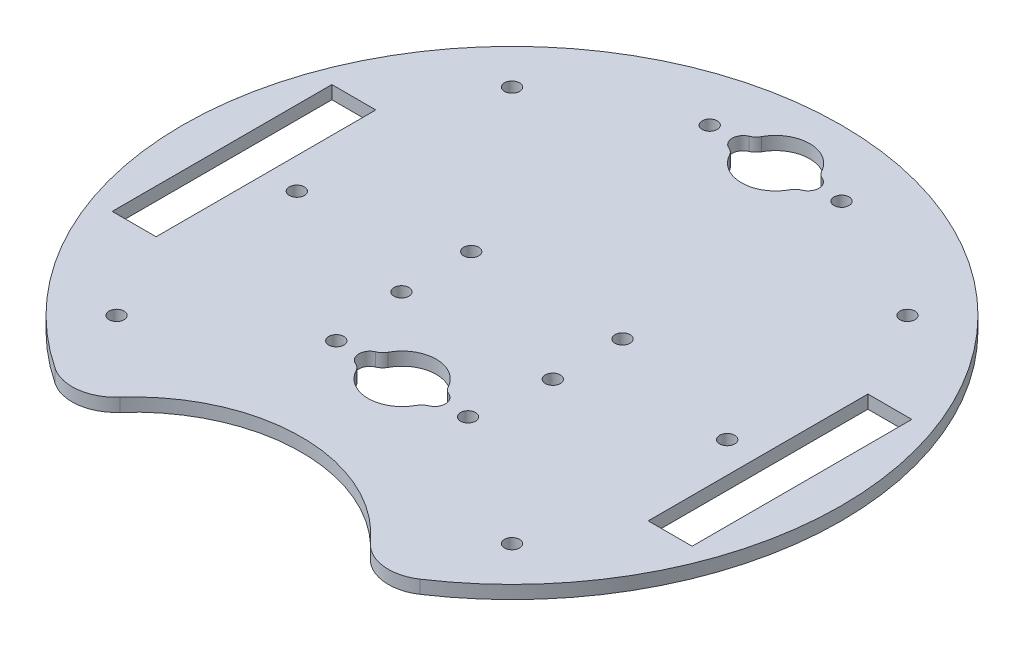
SolidWorks part; units mm, degrees
ref_plane "Front" through (0, 0, 0) normal (0, 0, 1) x (1, 0, 0)
ref_plane "Top" through (0, 0, 0) normal (0, 1, 0) x (1, 0, 0)
ref_plane "Right" through (0, 0, 0) normal (1, 0, 0) x (0, 0, -1)
sketch "Sketch1" plane through (0, 0, 0) normal (0, 1, 0) x (1, 0, 0)
  circle A0 centre (0, 0) radius 75
  dimension "D1" = 150
extrude "Boss-Extrude1" add sketch "Sketch1" along normal blind 3
sketch "Sketch2" plane through (0, 3, 0) normal (0, 1, 0) x (1, 0, 0)
  line L0 (-75, 0) -> (75, 0) construction
  line L2 (-66, -25) -> (-56, -25)
  line L3 (-66, -25) -> (-66, 25)
  line L4 (-66, 25) -> (-56, 25)
  line L5 (-56, -25) -> (-56, 25)
  line L6 (-66, -25) -> (-56, 25) construction
  line L7 (-66, 25) -> (-56, -25) construction
  line L8 (56, -25) -> (66, -25)
  line L9 (56, -25) -> (56, 25)
  line L10 (56, 25) -> (66, 25)
  line L11 (66, -25) -> (66, 25)
  line L12 (56, -25) -> (66, 25) construction
  line L13 (56, 25) -> (66, -25) construction
  circle A0 centre (0, 0) radius 75 construction
  point P5 (-61, 0)
  point P10 (61, 0)
  dimension "D1" = 50
  dimension "D2" = 50
  dimension "D3" = 10
  dimension "D4" = 10
  dimension "D5" = 61
  dimension "D6" = 61
extrude "Cut-Extrude1" cut sketch "Sketch2" against normal blind 6.35
sketch "Sketch3" plane through (0, 3, 0) normal (0, 1, 0) x (1, 0, 0)
  line L0 (0, 60) -> (0, -25) construction
  line L1 (-7.366, -25) -> (7.366, -25) construction
  line L2 (-7.366, 60) -> (7.366, 60) construction
  arc A0 (-7.3358, -27.4998) -> (7.3358, -27.4998) centre (0, -25) ccw
  arc A1 (-7.3358, -22.5002) -> (-7.3358, -27.4998) centre (-7.366, -25) ccw
  arc A2 (7.3358, -27.4998) -> (7.3358, -22.5002) centre (7.366, -25) ccw
  arc A3 (7.3358, -22.5002) -> (-7.3358, -22.5002) centre (0, -25) ccw
  arc A4 (-7.3358, 62.4998) -> (-7.3358, 57.5002) centre (-7.366, 60) ccw
  arc A5 (7.3358, 57.5002) -> (7.3358, 62.4998) centre (7.366, 60) ccw
  arc A6 (7.3358, 62.4998) -> (-7.3358, 62.4998) centre (0, 60) ccw
  arc A8 (-7.3358, 57.5002) -> (7.3358, 57.5002) centre (0, 60) ccw
  dimension "D1" = 15.5
  dimension "D3" = 14.732
  dimension "D4" = 5
  dimension "D2" = 15.5
  dimension "D5" = 5
  dimension "D6" = 60
  dimension "D7" = 25
  dimension "D8" = 14.732
extrude "Cut-Extrude2" cut sketch "Sketch3" against normal blind 10
sketch "Sketch4" plane through (0, 3, 0) normal (0, 1, 0) x (1, 0, 0)
  line L0 (0, 0) -> (0, -86.0323) construction
  line L1 (0, -86.0323) -> (33.1606, -67.2709) construction
  line L3 (-33.1606, -67.2709) -> (0, -86.0323) construction
  circle A0 centre (0, -86.0323) radius 38.1 construction
  circle A1 centre (0, 0) radius 75 construction
  arc A2 (-33.1606, -67.2709) -> (33.1606, -67.2709) centre (0, -86.0323) cw
  arc A3 (-33.1606, -67.2709) -> (33.1606, -67.2709) centre (0, 0) ccw
  dimension "D1" = 76.2
  dimension "D2" = 121
extrude "Cut-Extrude3" cut sketch "Sketch4" against normal blind 10 contours A2 A3
fillet "Fillet2" radius 10 2 edges at (33.1606, 1.5, 67.2709) (-33.1606, 1.5, 67.2709)
sketch "Sketch6" plane through (0, 3, 0) normal (0, 1, 0) x (1, 0, 0)
  line L0 (-15, 60) -> (15, 60) construction
  line L1 (0, 60) -> (0, 67.75) construction
  line L2 (0, 60) -> (0, 52.25) construction
  line L3 (0, -17.25) -> (0, -25) construction
  line L4 (0, -25) -> (0, -32.75) construction
  line L5 (-15, -25) -> (15, -25) construction
  line L6 (0, -17.25) -> (0, 0) construction
  line L31 (0, 52.25) -> (0, 0) construction
  circle A0 centre (-15, 60) radius 1.7145
  circle A1 centre (15, 60) radius 1.7145
  circle A6 centre (-15, -25) radius 1.7145
  circle A7 centre (15, -25) radius 1.7145
  circle A8 centre (0, -25) radius 7.75 construction
  circle A9 centre (0, 60) radius 7.75 construction
  dimension "D1" = 3.429
  dimension "D3" = 3.429
  dimension "D2" = 30
  dimension "D4" = 30
sketch "Sketch7" plane through (0, 3, 0) normal (0, 1, 0) x (1, 0, 0)
  line L0 (0, 75) -> (0, -47.9323) construction
  line L1 (-58.5, 0) -> (-48.975, 0) construction
  line L2 (17.225, 7.9375) -> (17.225, -7.9375) construction
  line L3 (-48.975, 0) -> (-17.225, 0) construction
  line L4 (-17.225, 7.9375) -> (-17.225, -7.9375) construction
  line L5 (-56, -25) -> (-56, 25) construction
  line L6 (48.975, 0) -> (17.225, 0) construction
  line L7 (58.5, 0) -> (48.975, 0) construction
  arc A0 (41.5307, -62.4516) -> (-41.5307, -62.4516) centre (0, 0) ccw construction
  arc A1 (28.5103, -60.7583) -> (-28.5103, -60.7583) centre (0, -86.0323) ccw construction
  circle A2 centre (-48.975, 0) radius 1.7145
  circle A3 centre (-17.225, 7.9375) radius 1.7145
  circle A4 centre (-17.225, -7.9375) radius 1.7145
  circle A5 centre (17.225, -7.9375) radius 1.7145
  circle A6 centre (17.225, 7.9375) radius 1.7145
  circle A7 centre (48.975, 0) radius 1.7145
  dimension "D1" = 3.429
  dimension "D2" = 9.525
  dimension "D3" = 31.75
  dimension "D4" = 15.875
  dimension "D5" = 2.5
extrude "Cut-Extrude5" cut sketch "Sketch7" against normal blind 3 contours A2 | A4 | A3 | A6 | A5 | A7
extrude "Cut-Extrude6" cut sketch "Sketch6" against normal blind 3
fillet "Fillet4" radius 3 8 edges at (-7.3358, 1.5, -57.5002) (7.3358, 1.5, -57.5002) (7.3358, 1.5, -62.4998) (-7.3358, 1.5, -62.4998) (7.3358, 1.5, 22.5002) (-7.3358, 1.5, 22.5002) (7.3358, 1.5, 27.4998) (-7.3358, 1.5, 27.4998)
sketch "Sketch8" plane through (0, 3, 0) normal (0, 1, 0) x (1, 0, 0)
  line L1 (45, -45) -> (-45, -45) construction
  line L2 (45, -45) -> (45, 45) construction
  line L3 (45, 45) -> (-45, 45) construction
  line L4 (-45, -45) -> (-45, 45) construction
  line L5 (45, -45) -> (-45, 45) construction
  line L6 (45, 45) -> (-45, -45) construction
  circle A0 centre (-45, 45) radius 1.7145
  circle A1 centre (45, 45) radius 1.7145
  circle A2 centre (45, -45) radius 1.7145
  circle A3 centre (-45, -45) radius 1.7145
  point P0 (0, 0)
  dimension "D3" = 3.429
  dimension "D1" = 90
  dimension "D2" = 90
extrude "Cut-Extrude7" cut sketch "Sketch8" against normal through all
